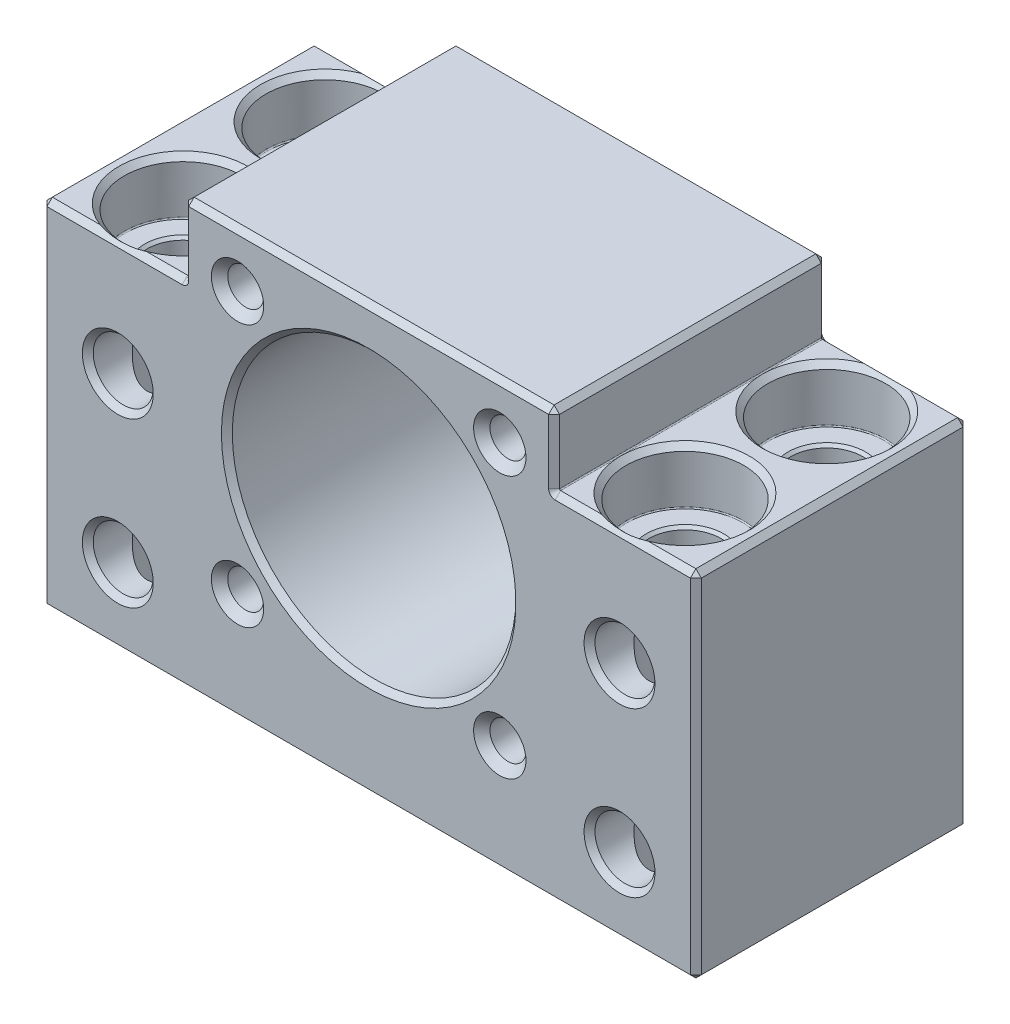
SolidWorks part; units mm, degrees
material "1023 Carbon Steel Sheet (SS)"
ref_plane "Front Plane" through (0, 0, 0) normal (0, 0, 1) x (1, 0, 0)
ref_plane "Top Plane" through (0, 0, 0) normal (0, 1, 0) x (1, 0, 0)
ref_plane "Right Plane" through (0, 0, 0) normal (1, 0, 0) x (0, 0, -1)
sketch "BK Body Sketch" plane through (0, 0, 0) normal (0, 0, 1) x (1, 0, 0)
  line L0 (30, -22) -> (-30, -22)
  line L1 (-30, -22) -> (-30, 10.5)
  line L2 (-30, 10.5) -> (-17, 10.5)
  line L3 (-17, 10.5) -> (-17, 17)
  line L4 (-17, 17) -> (17, 17)
  line L5 (17, 17) -> (17, 10.5)
  line L6 (17, 10.5) -> (30, 10.5)
  line L7 (30, 10.5) -> (30, -22)
  point P2 (0, -22)
  point P9 (0, 17)
  dimension "B" = 60
  dimension "B1" = 34
  dimension "H2" = 22
  dimension "H1" = 32.5
  dimension "H" = 39
extrude "BK Body" add sketch "BK Body Sketch" along normal mid plane 25
sketch "BK B-Flange" plane through (0, 0, 0) normal (0, 0, 1) x (1, 0, 0)
  circle A0 centre (0, 0) radius 11
  dimension "DOS" = 22
extrude "BK Flange" cut sketch "BK B-Flange" against normal through all both and the other way through all
sketch "BK B-Hole" plane through (0, 0, 12.5) normal (0, 0, 1) x (1, 0, 0)
  circle A0 centre (0, 0) radius 11 construction
  circle A1 centre (0, 0) radius 11
  circle A2 centre (0, 0) radius 13
  dimension "DO" = 26
extrude "BK Bearing" cut sketch "BK B-Hole" against normal offset from surface (20 mm away) 5 up to face at (11, 0, -12.5)
hole_wizard "Vertical Holes" positions "Sketch1" profile "Sketch2" counterbore size "M6" standard "ISO" end condition through all
sketch "Sketch1" plane through (0, 10.5, 0) normal (0, 1, 0) x (1, 0, 0)
  line L0 (23, 6.5) -> (-23, 6.5) construction
  line L3 (-17, 12.5) -> (-30, 12.5) construction
  point P0 (-23, 6.5)
  point P2 (-23, -6.5)
  point P4 (23, 6.5)
  point P6 (23, -6.5)
  point P11 (0, 6.5)
  dimension "P" = 46
  dimension "C1" = 13
  dimension "C2" = 6
sketch "Sketch2" plane through (-23, 10.5, -6.5) normal (1, 0, 0) x (0, 0, 1)
  line L0 (0, 0) -> (0, 32.5)
  line L1 (3.3, 32) -> (3.8, 32.5)
  line L2 (3.3, 32) -> (3.3, 5.25)
  line L3 (3.3, 5.25) -> (3.55, 5)
  line L4 (3.55, 5) -> (5.4, 5)
  line L5 (5.4, 5) -> (5.4, 0.5)
  line L6 (5.4, 0.5) -> (5.9, 0)
  line L7 (5.9, 0) -> (0, 0)
  line L8 (-5.4, 0.5) -> (-5.9, 0) construction
  line L9 (-3.3, 5.25) -> (-3.55, 5) construction
  line L11 (0, -6.35) -> (0, 107.95) construction
  line L12 (3.8, 32.5) -> (0, 32.5)
  line L13 (-3.3, 32) -> (-3.8, 32.5) construction
  dimension "Thru Hole Dia." = 6.6
  dimension "Thru Hole Depth" = 32.5
  dimension "C'Bore Dia." = 10.8
  dimension "C'Bore Depth" = 5
  dimension "Near C'Sink Dia." = 11.8
  dimension "Near C'Sink Angle" = 90
  dimension "Mid C'Sink Dia." = 7.1
  dimension "Mid C'Sink Angle" = 90
  dimension "Far C'Sink Dia." = 7.6
  dimension "Far C'Sink Angle" = 90
hole_wizard "Horizontal Holes" positions "Sketch3" profile "Sketch4" hole size "M5" standard "ISO" end condition through all
sketch "Sketch3" plane through (0, 0, 12.5) normal (0, 0, 1) x (1, 0, 0)
  line L0 (23, 0) -> (-23, 0) construction
  point P0 (-23, 0)
  point P2 (-23, -15)
  point P4 (23, 0)
  point P6 (23, -15)
  point P12 (0, 0)
  dimension "P" = 46
  dimension "E" = 15
sketch "Sketch4" plane through (-23, 0, 12.5) normal (1, 0, 0) x (0, -1, 0)
  line L0 (0, 0) -> (0, 25)
  line L1 (0, 25) -> (3.25, 25)
  line L2 (2.75, 24.5) -> (2.75, 0.5)
  line L3 (2.75, 0.5) -> (3.25, 0)
  line L5 (3.25, 0) -> (0, 0)
  line L6 (-2.75, 0.5) -> (-3.25, 0) construction
  line L7 (3.25, 25) -> (2.75, 24.5)
  line L8 (-3.25, 25) -> (-2.75, 24.5) construction
  line L11 (0, -6.35) -> (0, 107.95) construction
  dimension "Near C'Sink Angle" = 90
  dimension "Far C'Sink Angle" = 90
  dimension "Thru Hole Dia." = 5.5
  dimension "Thru Hole Depth" = 25
  dimension "Near C'Sink Dia." = 6.5
  dimension "Far C'Sink Dia." = 6.5
hole_wizard "Flange Holes" positions "Sketch5" profile "Sketch6" tap size "M4" standard "ISO"
sketch "Sketch5" plane through (0, 0, 12.5) normal (0, 0, 1) x (1, 0, 0)
  line L0 (12.0208, 12.0208) -> (-12.0208, -12.0208) construction
  line L1 (-12.0208, -12.0208) -> (-12.0208, 12.0208) construction
  line L3 (12.0208, 12.0208) -> (-12.0208, 12.0208) construction
  point P0 (-12.0208, 12.0208)
  point P2 (12.0208, 12.0208)
  point P4 (12.0208, -12.0208)
  point P6 (-12.0208, -12.0208)
  point P13 (0, 0)
  dimension "rf" = 34
sketch "Sketch6" plane through (-12.0208, 12.0208, 12.5) normal (1, 0, 0) x (0, -1, 0)
  line L0 (0, 0) -> (0, 12.4914)
  line L1 (0, 12.4914) -> (1.65, 11.5)
  line L2 (1.65, 11.5) -> (1.65, 0.75)
  line L3 (1.65, 0.75) -> (2.4, 0)
  line L5 (2.4, 0) -> (0, 0)
  line L6 (-1.65, 0.75) -> (-2.4, 0) construction
  line L10 (0, 12.4914) -> (-1.65, 11.5) construction
  line L11 (0, -6.35) -> (0, 107.95) construction
  dimension "Near C'Sink Angle" = 90
  dimension "Tap Drill Dia." = 3.3
  dimension "Tap Drill Depth" = 11.5
  dimension "Near C'Sink Dia." = 4.8
  dimension "Drill Angle" = 118
cosmetic thread "Hole Thread1" parameters "D1"=8, "D2"=4
cosmetic thread "Hole Thread2" parameters "D1"=8, "D2"=4
cosmetic thread "Hole Thread3" parameters "D1"=8, "D2"=4
cosmetic thread "Hole Thread4" parameters "D1"=8, "D2"=4
fillet "Bearing Fillet" radius 0.15 1 edges at (-13, 0, -7.5)
fillet "Production Fillet" radius 0.1 6 edges at (-17, 10.5, 0) (17, 10.5, 0) (-23, 5.5, 11.9) (-23, 5.5, -1.1) (23, 5.5, 11.9) (23, 5.5, -1.1)
chamfer "Aesthetic Chamfer" distance 0.5 angle 45 29 edges at (17, 17, 0) (0, 17, 12.5) (-17, 17, 0) (0, 17, -12.5) (-17, 13.8, -12.5) (17, 13.8, -12.5) (17, 13.8, 12.5) (-17, 13.8, 12.5) (-17.0293, 10.5293, -12.5) (17.0293, 10.5293, -12.5) (17.0293, 10.5293, 12.5) (-17.0293, 10.5293, 12.5) (-30, 10.5, 0) (-30, -22, 0) (-23.55, 10.5, -12.5) (-30, -5.75, -12.5) (30, -22, 0) (0, -22, -12.5) (30, -5.75, -12.5) (23.55, 10.5, -12.5) (30, 10.5, 0) (23.55, 10.5, 12.5) (30, -5.75, 12.5) (0, -22, 12.5) (-30, -5.75, 12.5) (-23.55, 10.5, 12.5) (11, 0, -12.5) (-11, 0, -7.5) (13, 0, 12.5)
equation "\"Near C'Sink Dia.@Sketch2\"= \"C'Bore Dia.@Sketch2\" + 1"
equation "\"Mid C'Sink Dia.@Sketch2\"= \"Thru Hole Dia.@Sketch2\" + 0.5"
equation "\"Far C'Sink Dia.@Sketch2\"= \"Thru Hole Dia.@Sketch2\" + 1"
equation "\"rf@Sketch5\"= 2 * ( \"H@BK Body Sketch\" - \"H2@BK Body Sketch\" )'Flange Holes distance"
equation "\"Far C'Sink Dia.@Sketch4\"= \"Thru Hole Dia.@Sketch4\" + 1"
equation "\"Near C'Sink Dia.@Sketch6\"= \"Tap Drill Dia.@Sketch6\" + 1.5"
